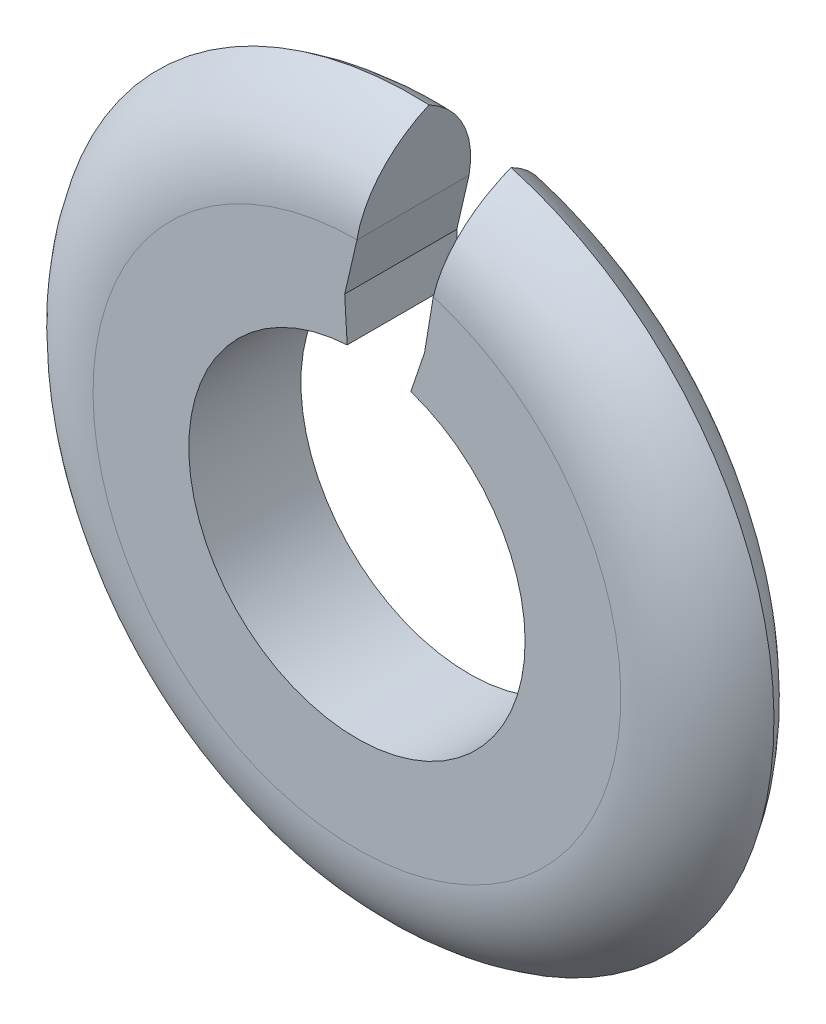
SolidWorks part; units mm, degrees
material "1023 Листовая углеродистая сталь (SS)"
ref_plane "Спереди" through (0, 0, 0) normal (0, 0, 1) x (1, 0, 0)
ref_plane "Сверху" through (0, 0, 0) normal (0, 1, 0) x (1, 0, 0)
ref_plane "Справа" through (0, 0, 0) normal (1, 0, 0) x (0, 0, -1)
sketch "Эскиз1" plane through (0, 0, 0) normal (0, 0, 1) x (1, 0, 0)
  line L0 (-0.0871, 1.4975) -> (-0.1093, 1.879)
  line L1 (0.6032, 1.783) -> (0.4807, 1.4209)
  line L2 (-0.1093, 1.879) -> (0, 2.3518)
  line L3 (0.6032, 1.783) -> (0.6805, 2.2512)
  line L4 (0, 2.3518) -> (0.1649, 3.3501)
  line L5 (0.6805, 2.2512) -> (0.9055, 3.2296)
  arc A0 (-0.0871, 1.4975) -> (0.4807, 1.4209) centre (0, 0) ccw
  circle A3 centre (0, 0) radius 3.3541
  dimension "D1" = 3
extrude "Бобышка-Вытянуть1" add sketch "Эскиз1" along normal blind 1 contours L4 A3 L5 L3 L1 A0 L0 L2 region at (-0.2132, -1.5806, 0)
fillet "Скругление4" radius 1 2 edges at (-0.5385, -3.3106, 0) (-0.5385, -3.3106, 1)
